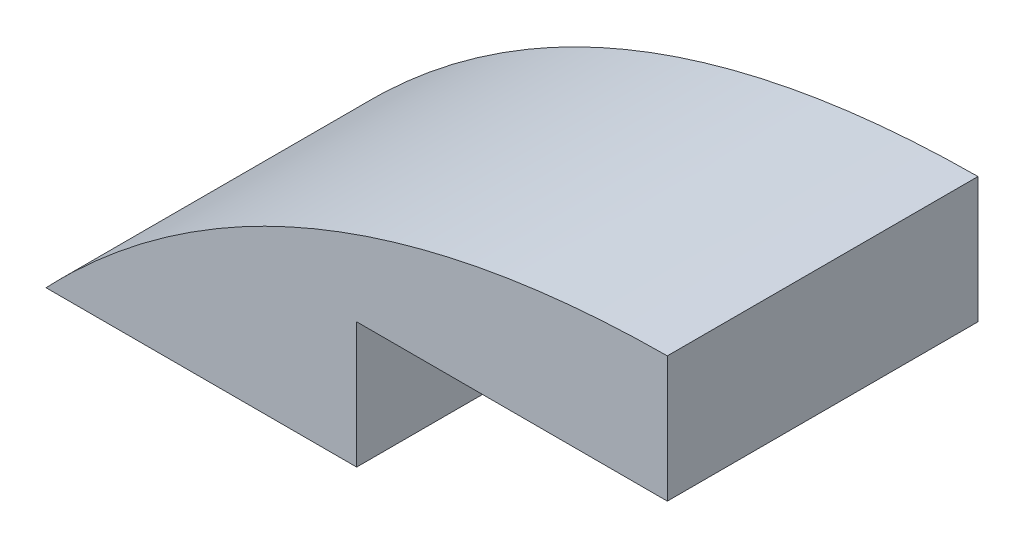
SolidWorks part; units mm, degrees
ref_plane "Front Plane" through (0, 0, 0) normal (0, 0, 1) x (1, 0, 0)
ref_plane "Top Plane" through (0, 0, 0) normal (0, 1, 0) x (1, 0, 0)
ref_plane "Right Plane" through (0, 0, 0) normal (1, 0, 0) x (0, 0, -1)
sketch "Sketch2" plane through (0, 0, 0) normal (0, 1, 0) x (1, 0, 0)
  line L1 (0, 0) -> (7.9, 0)
  line L2 (0, 0) -> (0, 7.9)
  line L3 (0, 7.9) -> (7.9, 7.9)
  line L4 (7.9, 0) -> (7.9, 7.9)
  dimension "D1" = 7.9
  dimension "D2" = 7.9
extrude "Boss-Extrude1" add sketch "Sketch2" along normal blind 3.2
sketch "Sketch3" plane through (0, 3.2, 0) normal (0, 1, 0) x (1, 0, 0)
  line L1 (7.9, 7.9) -> (15.8, 7.9)
  line L2 (7.9, 7.9) -> (7.9, 0)
  line L3 (7.9, 0) -> (15.8, 0)
  line L4 (15.8, 7.9) -> (15.8, 0)
  dimension "D1" = 7.9
extrude "Boss-Extrude2" add sketch "Sketch3" along normal blind 3.2 separate body
sketch "Sketch4" plane through (0, 0, -7.9) normal (0, 0, -1) x (-1, 0, 0)
  line L0 (-15.8, 6.4) -> (0, 6.4)
  line L1 (0, 6.4) -> (0, 0)
  spline S0 degree 2 poles (-15.8, 6.4) (-6.036, 6.3402) (0, 0) knots 0 0 0 1 1 1
sketch "Sketch7" plane through (7.9, 0, 0) normal (-1, 0, 0) x (0, 0, 1)
  line L1 (0, 3.2) -> (-7.9, 3.2)
  line L2 (0, 3.2) -> (0, 6.4)
  line L3 (0, 6.4) -> (-7.9, 6.4)
  line L4 (-7.9, 3.2) -> (-7.9, 6.4)
extrude "Boss-Extrude5" add sketch "Sketch7" along normal blind 7.2
extrude "Cut-Extrude2" cut sketch "Sketch4" against normal blind 8.2
